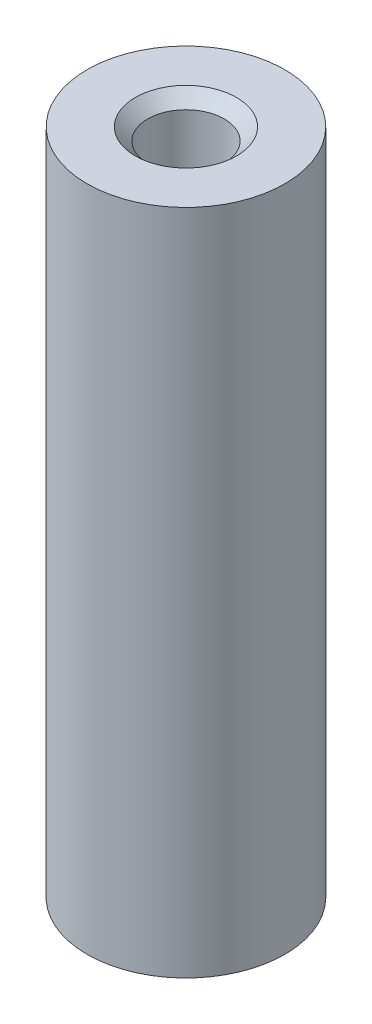
SolidWorks part; units mm, degrees
ref_plane "Ebene vorne" through (0, 0, 0) normal (0, 0, 1) x (1, 0, 0)
ref_plane "Ebene oben" through (0, 0, 0) normal (0, 1, 0) x (1, 0, 0)
ref_plane "Ebene rechts" through (0, 0, 0) normal (1, 0, 0) x (0, 0, -1)
sketch "Skizze1" plane through (0, 0, 0) normal (0, 1, 0) x (1, 0, 0)
  circle A0 centre (0, 0) radius 4
  dimension "D1" = 8
extrude "Aufsatz-Linear austragen1" add sketch "Skizze1" along normal blind 27
hole_wizard "Ø3.1 (3.1) Durchmesser Bohrung1" positions "Skizze2" profile "Skizze3" hole size "Ø3.1" standard "ISO" end condition through all
sketch "Skizze2" plane through (0, 27, 0) normal (0, 1, 0) x (1, 0, 0)
  point P0 (0, 0)
sketch "Skizze3" plane through (0, 27, 0) normal (1, 0, 0) x (0, 0, 1)
  line L0 (0, 0) -> (0, 27)
  line L1 (0, 27) -> (1.55, 27)
  line L2 (1.55, 27) -> (1.55, 0)
  line L5 (1.55, 0) -> (0, 0)
  line L11 (0, -6.35) -> (0, 107.95) construction
  dimension "Bohrerdurchmesser" = 3.1
  dimension "Bohrungstiefe" = 27
chamfer "Fase1" distance 0.5 angle 45 2 edges at (0, 0, 1.55) (0, 27, 1.55)
